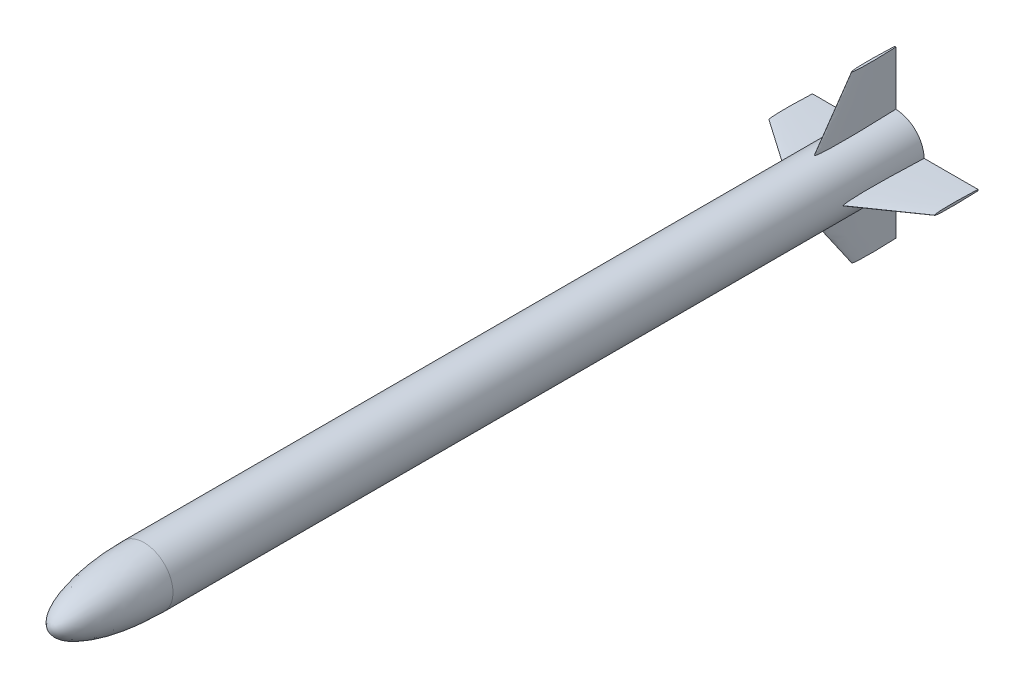
SolidWorks part; units mm, degrees
ref_plane "Front Plane" through (0, 0, 0) normal (0, 0, 1) x (1, 0, 0)
ref_plane "Top Plane" through (0, 0, 0) normal (0, 1, 0) x (1, 0, 0)
ref_plane "Right Plane" through (0, 0, 0) normal (1, 0, 0) x (0, 0, -1)
sketch "Sketch2" plane through (0, 0, 0) normal (1, 0, 0) x (0, 0, -1)
  line L0 (254, 78.3229) -> (2289.4925, 78.3229)
  line L1 (2289.4925, 78.3229) -> (2289.4925, 0)
  line L2 (2289.4925, 0) -> (0, 0)
  line L3 (0, 0) -> (-254, 0) construction
  line L4 (0, 0) -> (2.1037, 78.3229) construction
  ellipse E0 centre (254, 0) end of major axis (0, 0) minor radius 78.3229 (254, 78.3229) -> (0, 0) ccw
  dimension "D1" = 2035.4925
  dimension "D2" = 254
  dimension "D3" = 78.3229
  dimension "D5" = 254
  dimension "D4" = 78.3229
revolve "Revolve1" add sketch "Sketch2" angle 360 about L2
sketch "Sketch3" plane through (0, 0, -2289.4925) normal (0, 0, -1) x (-1, 0, 0)
  circle A0 centre (0, 0) radius 43.942
  dimension "D1" = 87.884
extrude "Boss-Extrude1" add sketch "Sketch3" along normal blind 15.24
ref_plane "Plane1" through (0, 254, 0) normal (0, 1, 0) x (1, 0, 0)
sketch "Sketch4" plane through (0, 254, 0) normal (0, 1, 0) x (1, 0, 0)
  line L1 (-1.5875, 2083.1175) -> (1.5875, 2083.1175)
  line L2 (-1.5875, 2083.1175) -> (-1.5875, 2286.3175)
  line L3 (-1.5875, 2286.3175) -> (1.5875, 2286.3175)
  line L4 (1.5875, 2083.1175) -> (1.5875, 2286.3175)
  line L5 (78.3229, 2289.4925) -> (-78.3229, 2289.4925) construction
  point P6 (0, 2286.3175)
  dimension "D1" = 3.175
  dimension "D2" = 3.175
  dimension "D3" = 203.2
extrude "Boss-Extrude2" add sketch "Sketch4" against normal up to surface (175.6932 mm away) up to face at (-78.3229, 0, -254)
sketch "Sketch5" plane through (-1.5875, 0, 0) normal (-1, 0, 0) x (0, 0, 1)
  line L0 (-2286.3175, 224.3568) -> (-2184.7175, 224.3568)
  line L1 (-2286.3175, 78.3068) -> (-2286.3175, 254) construction
  line L2 (-2184.7175, 224.3568) -> (-2083.1175, 78.3068)
  line L3 (-2083.1175, 78.3068) -> (-2083.1175, 254)
  line L4 (-2083.1175, 254) -> (-2286.3175, 254)
  line L5 (-2286.3175, 254) -> (-2286.3175, 224.3568)
  dimension "D1" = 101.6
  dimension "D2" = 146.05
extrude "Cut-Extrude1" cut sketch "Sketch5" against normal up to next
sketch "Sketch6" plane through (0, 224.3568, 0) normal (0, 1, 0) x (1, 0, 0)
  line L0 (0, 2324.1) -> (0, 2171.7) construction
  spline S0 degree 4 poles (0, 2171.7) (0.051, 2171.7006) (0.1231, 2171.7139) (0.2087, 2171.7542) (0.3062, 2171.8284) (0.3808, 2171.9014) (0.4592, 2171.9956) (0.5527, 2172.1319) (0.6711, 2172.3415) (0.8367, 2172.7057) (1.0914, 2173.434) (1.3865, 2174.6081) (1.6836, 2176.1867) (2.0477, 2178.6899) (2.3957, 2181.9018) (2.8436, 2187.452) (3.2338, 2195.3473) (3.4845, 2204.9737) (3.5657, 2216.3247) (3.4973, 2227.6786) (3.3169, 2239.0263) (3.0506, 2250.3803) (2.7588, 2260.3008) (2.4732, 2268.8226) (2.1645, 2277.3095) (1.8846, 2284.4423) (1.593, 2291.4551) (1.2729, 2298.6554) (1.0213, 2304.1337) (0.7286, 2310.1507) (0.4762, 2315.2186) (0.091, 2322.4894) (-0.1374, 2326.6114) (-0.4882, 2332.7319) (-0.6703, 2335.6828) (-0.8182, 2338.1424) (-0.8568, 2338.7185) (-0.8967, 2339.3772) knots 0 0 0 0 0 0.001189 0.001745 0.002211 0.002902 0.003665 0.004655 0.006135 0.008619 0.013162 0.022972 0.034881 0.04679 0.073274 0.099757 0.167217 0.234678 0.302138 0.369599 0.437059 0.504519 0.57198 0.60571 0.63944 0.7069 0.74063 0.774361 0.808091 0.841821 0.875551 0.909281 0.954641 0.97732 0.98866 1 1 1 1 1 construction
  spline S1 degree 4 poles (0, 2171.7) (0.051, 2171.7006) (0.1231, 2171.7139) (0.2087, 2171.7542) (0.3062, 2171.8284) (0.3808, 2171.9014) (0.4592, 2171.9956) (0.5527, 2172.1319) (0.6711, 2172.3415) (0.8367, 2172.7057) (1.0914, 2173.434) (1.3865, 2174.6081) (1.6836, 2176.1867) (2.0477, 2178.6899) (2.3957, 2181.9018) (2.8436, 2187.452) (3.2338, 2195.3473) (3.4845, 2204.9737) (3.5657, 2216.3247) (3.4973, 2227.6786) (3.3169, 2239.0263) (3.0506, 2250.3803) (2.7588, 2260.3008) (2.4732, 2268.8226) (2.1645, 2277.3095) (1.8846, 2284.4423) (1.593, 2291.4551) (1.2729, 2298.6554) (1.0213, 2304.1337) (0.7286, 2310.1507) (0.4762, 2315.2186) (0.2102, 2320.239) (0.0709, 2322.8117) (0, 2324.1) knots 0 0 0 0 0 0.001189 0.001745 0.002211 0.002902 0.003665 0.004655 0.006135 0.008619 0.013162 0.022972 0.034881 0.04679 0.073274 0.099757 0.167217 0.234678 0.302138 0.369599 0.437059 0.504519 0.57198 0.60571 0.63944 0.7069 0.74063 0.774361 0.808091 0.841821 0.875551 0.909281 0.909281 0.909281 0.909281 0.909281
  spline S2 degree 4 poles (0, 2171.7) (-0.051, 2171.7006) (-0.1231, 2171.7139) (-0.2087, 2171.7542) (-0.3062, 2171.8284) (-0.3808, 2171.9014) (-0.4592, 2171.9956) (-0.5527, 2172.1319) (-0.6711, 2172.3415) (-0.8367, 2172.7057) (-1.0914, 2173.434) (-1.3865, 2174.6081) (-1.6836, 2176.1867) (-2.0477, 2178.6899) (-2.3957, 2181.9018) (-2.8436, 2187.452) (-3.2338, 2195.3473) (-3.4845, 2204.9737) (-3.5657, 2216.3247) (-3.4973, 2227.6786) (-3.3169, 2239.0263) (-3.0506, 2250.3803) (-2.7588, 2260.3008) (-2.4732, 2268.8226) (-2.1645, 2277.3095) (-1.8846, 2284.4423) (-1.593, 2291.4551) (-1.2729, 2298.6554) (-1.0213, 2304.1337) (-0.7286, 2310.1507) (-0.4762, 2315.2186) (-0.2102, 2320.239) (-0.0709, 2322.8117) (0, 2324.1) knots 0 0 0 0 0 0.001189 0.001745 0.002211 0.002902 0.003665 0.004655 0.006135 0.008619 0.013162 0.022972 0.034881 0.04679 0.073274 0.099757 0.167217 0.234678 0.302138 0.369599 0.437059 0.504519 0.57198 0.60571 0.63944 0.7069 0.74063 0.774361 0.808091 0.841821 0.875551 0.909281 0.909281 0.909281 0.909281 0.909281
ref_plane "Plane2" through (0, 78.105, 0) normal (0, 1, 0) x (1, 0, 0)
sketch "Sketch7" plane through (0, 78.105, 0) normal (0, 1, 0) x (1, 0, 0)
  line L0 (0, 2324.1) -> (0, 2070.1) construction
  spline S0 degree 4 poles (0, 2070.1) (0.0342, 2070.1002) (0.1014, 2070.1073) (0.2316, 2070.1502) (0.3603, 2070.247) (0.4625, 2070.3536) (0.562, 2070.481) (0.6446, 2070.6032) (0.7505, 2070.7852) (0.8922, 2071.0745) (1.0839, 2071.5498) (1.3694, 2072.4381) (1.8161, 2074.2937) (2.2988, 2077.1802) (2.77, 2080.9905) (3.2968, 2086.605) (3.7697, 2093.44) (4.2835, 2103.6731) (4.696, 2117.3079) (4.925, 2133.2199) (4.9497, 2151.4074) (4.8018, 2169.593) (4.557, 2185.5057) (4.283, 2199.1414) (3.9649, 2212.7806) (3.6673, 2224.1378) (3.3402, 2235.5096) (2.9883, 2246.8566) (2.6904, 2255.9678) (2.3035, 2267.2859) (1.805, 2280.9991) (1.282, 2294.483) (0.7524, 2307.184) (0.3684, 2315.9782) (0.0635, 2322.737) (-0.1342, 2327.0197) (-0.4722, 2334.1824) (-0.736, 2339.5059) (-1.0136, 2345.0628) (-1.1551, 2347.7422) (-1.2484, 2349.5509) knots 0 0 0 0 0 0.000483 0.000965 0.00193 0.00226 0.00259 0.00327 0.004035 0.005264 0.007185 0.010582 0.017344 0.032491 0.048939 0.065387 0.097843 0.130299 0.19521 0.260121 0.325033 0.389944 0.454856 0.487311 0.519767 0.584679 0.617134 0.64959 0.682046 0.714502 0.779413 0.844324 0.87678 0.893008 0.909236 0.931927 0.954618 0.977309 1 1 1 1 1 construction
  spline S1 degree 4 poles (0, 2070.1) (0.0342, 2070.1002) (0.1014, 2070.1073) (0.2316, 2070.1502) (0.3603, 2070.247) (0.4625, 2070.3536) (0.562, 2070.481) (0.6446, 2070.6032) (0.7505, 2070.7852) (0.8922, 2071.0745) (1.0839, 2071.5498) (1.3694, 2072.4381) (1.8161, 2074.2937) (2.2988, 2077.1802) (2.77, 2080.9905) (3.2968, 2086.605) (3.7697, 2093.44) (4.2835, 2103.6731) (4.696, 2117.3079) (4.925, 2133.2199) (4.9497, 2151.4074) (4.8018, 2169.593) (4.557, 2185.5057) (4.283, 2199.1414) (3.9649, 2212.7806) (3.6673, 2224.1378) (3.3402, 2235.5096) (2.9883, 2246.8566) (2.6904, 2255.9678) (2.3035, 2267.2859) (1.805, 2280.9991) (1.282, 2294.483) (0.7524, 2307.184) (0.3684, 2315.9782) (0.1425, 2320.9863) (0.0475, 2323.0676) (0, 2324.1) knots 0 0 0 0 0 0.000483 0.000965 0.00193 0.00226 0.00259 0.00327 0.004035 0.005264 0.007185 0.010582 0.017344 0.032491 0.048939 0.065387 0.097843 0.130299 0.19521 0.260121 0.325033 0.389944 0.454856 0.487311 0.519767 0.584679 0.617134 0.64959 0.682046 0.714502 0.779413 0.844324 0.87678 0.893008 0.909236 0.909236 0.909236 0.909236 0.909236
  spline S2 degree 4 poles (0, 2070.1) (-0.0342, 2070.1002) (-0.1014, 2070.1073) (-0.2316, 2070.1502) (-0.3603, 2070.247) (-0.4625, 2070.3536) (-0.562, 2070.481) (-0.6446, 2070.6032) (-0.7505, 2070.7852) (-0.8922, 2071.0745) (-1.0839, 2071.5498) (-1.3694, 2072.4381) (-1.8161, 2074.2937) (-2.2988, 2077.1802) (-2.77, 2080.9905) (-3.2968, 2086.605) (-3.7697, 2093.44) (-4.2835, 2103.6731) (-4.696, 2117.3079) (-4.925, 2133.2199) (-4.9497, 2151.4074) (-4.8018, 2169.593) (-4.557, 2185.5057) (-4.283, 2199.1414) (-3.9649, 2212.7806) (-3.6673, 2224.1378) (-3.3402, 2235.5096) (-2.9883, 2246.8566) (-2.6904, 2255.9678) (-2.3035, 2267.2859) (-1.805, 2280.9991) (-1.282, 2294.483) (-0.7524, 2307.184) (-0.3684, 2315.9782) (-0.1425, 2320.9863) (-0.0475, 2323.0676) (0, 2324.1) knots 0 0 0 0 0 0.000483 0.000965 0.00193 0.00226 0.00259 0.00327 0.004035 0.005264 0.007185 0.010582 0.017344 0.032491 0.048939 0.065387 0.097843 0.130299 0.19521 0.260121 0.325033 0.389944 0.454856 0.487311 0.519767 0.584679 0.617134 0.64959 0.682046 0.714502 0.779413 0.844324 0.87678 0.893008 0.909236 0.909236 0.909236 0.909236 0.909236
loft "Loft12" add profiles "Sketch6", "Sketch7" connector at (0, 224.3568, -2171.7) connector at (0, 78.105, -2070.1)
sketch "Sketch8" plane through (0, 78.105, 0) normal (0, -1, 0) x (1, 0, 0)
  line L0 (-1.4702, -2289.4925) -> (1.4702, -2289.4925) construction
  line L1 (-4.9625, -2289.4925) -> (2.5426, -2289.4925)
  line L2 (-4.9625, -2289.4925) -> (-4.9625, -2339.479)
  line L3 (-4.9625, -2339.479) -> (2.5426, -2339.479)
  line L4 (2.5426, -2289.4925) -> (2.5426, -2339.479)
extrude "Cut-Extrude3" cut sketch "Sketch8" against normal through all
pattern_circular "CirPattern1" count 4 over 360 about axis through (0, 0, -2289.4925) along (0, 0, -1) of "Boss-Extrude2", "Cut-Extrude1", "Loft12", "Cut-Extrude3"
equation "\"Body Tube Length\"= 80.1375"
equation "\"D1@Sketch2\"=\"Body Tube Length\""
equation "\"Retainer Diameter\"= 3.46"
equation "\"D1@Sketch3\"=\"Retainer Diameter\""
equation "\"Retainer Height\"= 0.6"
equation "\"D1@Boss-Extrude1\"=\"Retainer Height\""
equation "\"Fin Offset\"= .125"
equation "\"D1@Sketch4\"=\"Fin Offset\""
equation "\"Fin Thickness\"= .125"
equation "\"D2@Sketch4\"=\"Fin Thickness\""
equation "\"Fin Root Chord\"= 8"
equation "\"D3@Sketch4\"=\"Fin Root Chord\""
equation "\"Fin Tip Chord\"= 4"
equation "\"D1@Sketch5\"=\"Fin Tip Chord\""
equation "\"Fin Height\"= 5.75"
equation "\"D2@Sketch5\"=\"Fin Height\""
equation "\"Fin Epoxy Fillet Radius\"=0.1"
equation "\"Nosecone Length\"= 10"
equation "\"D2@Sketch2\"=\"Nosecone Length\""
equation "\"Rocket Radius\"=3.08358"
equation "\"D3@Sketch2\"= \"Rocket Radius\""
equation "\"D5@Sketch2\"=\"Nosecone Length\""
equation "\"D4@Sketch2\"=\"Rocket Radius\""
